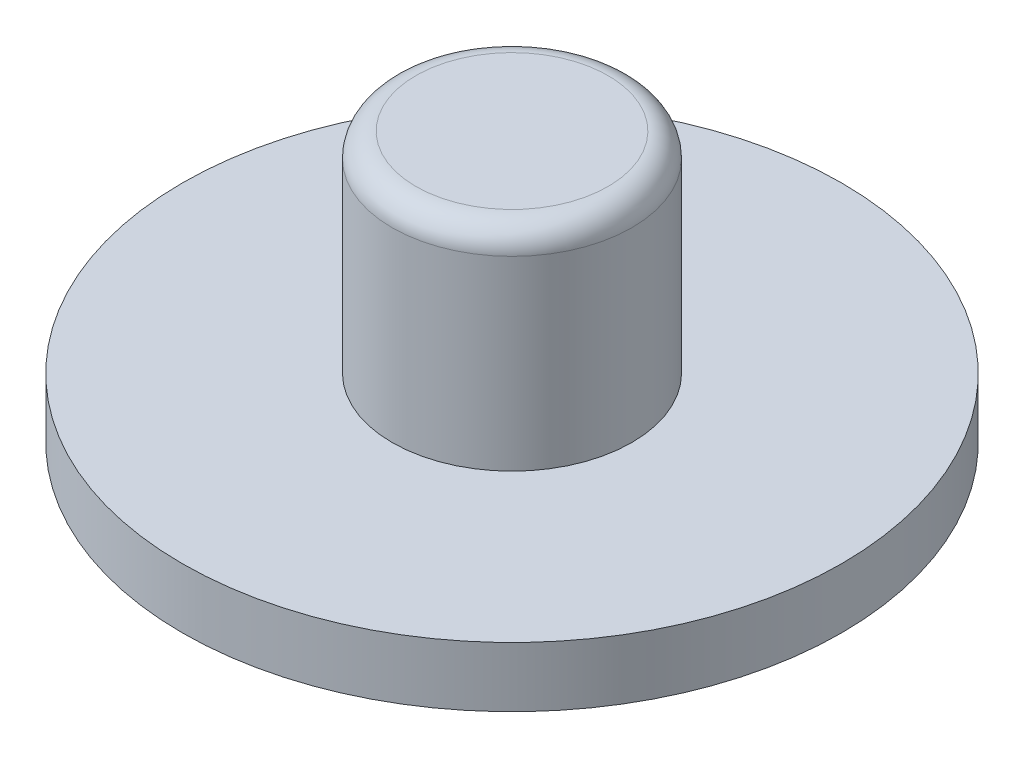
SolidWorks part; units mm, degrees
ref_plane "Front Plane" through (0, 0, 0) normal (0, 0, 1) x (1, 0, 0)
ref_plane "Top Plane" through (0, 0, 0) normal (0, 1, 0) x (1, 0, 0)
ref_plane "Right Plane" through (0, 0, 0) normal (1, 0, 0) x (0, 0, -1)
sketch "Sketch1" plane through (0, 0, 0) normal (0, 1, 0) x (1, 0, 0)
  circle A0 centre (0, 0) radius 4
  dimension "D1" = 8
extrude "Boss-Extrude1" add sketch "Sketch1" along normal mid plane 7
fillet "Fillet1" radius 0.7937 1 edges at (0, 3.5, 4)
sketch "Sketch2" plane through (0, -3.5, 0) normal (0, -1, 0) x (1, 0, 0)
  circle A0 centre (0, 0) radius 11
  dimension "D1" = 22
extrude "Boss-Extrude2" add sketch "Sketch2" along normal blind 2
